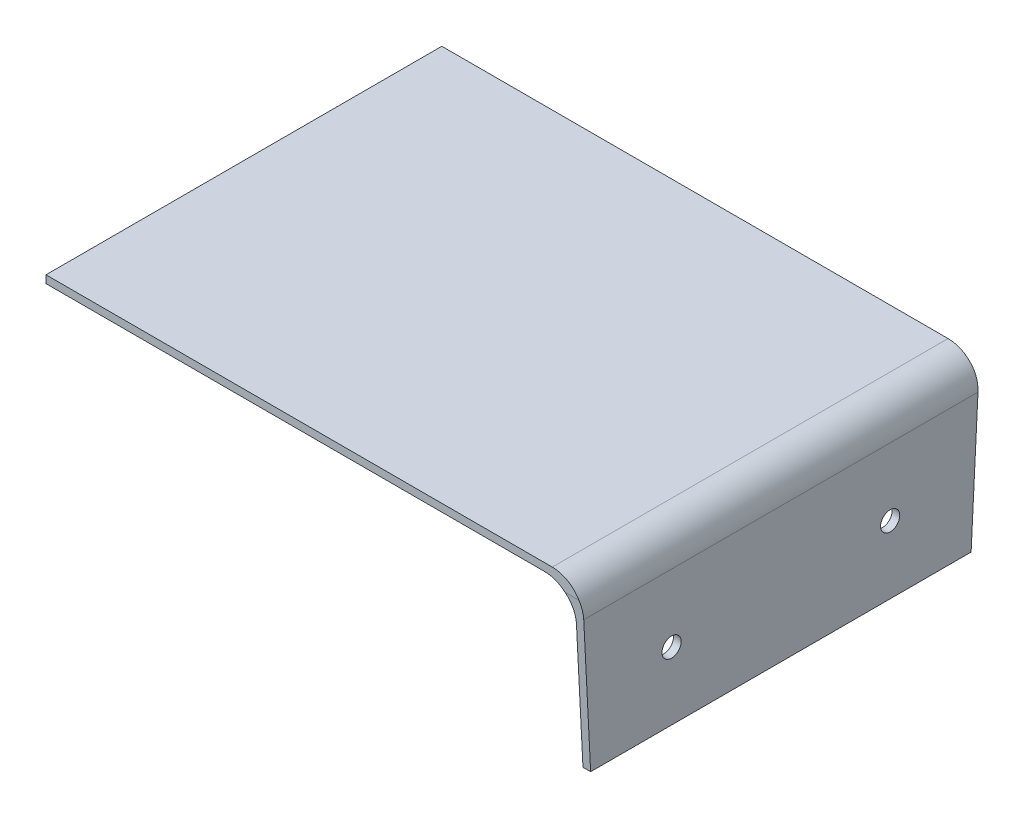
SolidWorks part; units mm, degrees
ref_plane "Front Plane" through (0, 0, 0) normal (0, 0, 1) x (1, 0, 0)
ref_plane "Top Plane" through (0, 0, 0) normal (0, 1, 0) x (1, 0, 0)
ref_plane "Right Plane" through (0, 0, 0) normal (1, 0, 0) x (0, 0, -1)
sketch "Sketch1" plane through (0, 0, 0) normal (0, 0, 1) x (1, 0, 0)
  line L0 (-22.4971, 23.5) -> (-22.4971, 22.4986)
  line L1 (42.6046, 22.4986) -> (46.5, 22.4986)
  line L2 (42.6046, 22.4986) -> (-22.4971, 22.4986)
  line L3 (46.5029, 18.5) -> (46.5029, 1.8932)
  line L4 (46.5029, 1.8932) -> (47.5029, 1.8932)
  line L5 (46.5, 22.4986) -> (46.5029, 18.5)
  line L6 (47.5029, 1.8932) -> (47.5029, 18.5)
  line L7 (-22.4971, 23.5) -> (42.5, 23.5)
  line L8 (47.5029, 18.5) -> (47.5029, 23.5)
  line L9 (47.5029, 23.5) -> (42.5, 23.5)
  dimension "D1" = 1
  dimension "D2" = 1.0014
  dimension "D3" = 70
extrude "Boss-Extrude1" add sketch "Sketch1" along normal blind 51.6
sketch "Sketch3" plane through (47.5029, 0, 0) normal (1, 0, 0) x (0, 0, -1)
  line L0 (-51.6, 21.5) -> (-51.6, 1.8932)
  line L1 (-51.6, 1.8932) -> (-51.6, 23.5) construction
  line L2 (-51.6, 1.8932) -> (-50.6, 1.8932)
  line L3 (-51.6, 1.8932) -> (0, 1.8932) construction
  line L4 (-50.6, 1.8932) -> (-51.6, 21.5)
  line L5 (0, 21.5) -> (-1, 1.8932)
  line L6 (0, 22.4986) -> (0, 18.5) construction
  line L7 (-1, 1.8932) -> (0, 1.8932)
  line L8 (0, 1.8932) -> (0, 21.5)
  line L10 (-51.6, 23.5) -> (0, 23.5) construction
  dimension "D1" = 2
  dimension "D2" = 1
  dimension "D3" = 1
  dimension "D4" = 2
extrude "Cut-Extrude1" cut sketch "Sketch3" against normal blind 10
fillet "Fillet3" radius 4 2 edges at (46.5, 22.4986, 25.8) (47.5029, 23.5, 25.8)
sketch "Sketch4" plane through (0, 22.4986, 0) normal (0, -1, 0) x (1, 0, 0)
  line L0 (-22.4971, 51.6) -> (-22.4971, 0) construction
  line L1 (-22.4971, 15) -> (-17.4971, 15)
  line L2 (-22.4971, 15) -> (-22.4971, 36.6)
  line L3 (-22.4971, 36.6) -> (-17.4971, 36.6)
  line L4 (-17.4971, 15) -> (-17.4971, 36.6)
  line L5 (-22.4971, 51.6) -> (42.5029, 51.6) construction
  line L6 (42.6046, 0) -> (-22.4971, 0) construction
  dimension "D1" = 5
  dimension "D2" = 15
  dimension "D3" = 15
extrude "Boss-Extrude2" add sketch "Sketch4" along normal blind 2.5
sketch "Sketch5" plane through (-22.4971, 0, 0) normal (-1, 0, 0) x (0, 0, 1)
  line L0 (36.6, 19.9986) -> (15, 19.9986) construction
  line L1 (36.6, 19.9986) -> (15, 19.9986)
  line L2 (36.6, 19.9986) -> (36.6, 21.4986)
  line L3 (36.6, 21.4986) -> (15, 21.4986)
  line L4 (15, 19.9986) -> (15, 21.4986)
  line L5 (15, 19.9986) -> (15, 22.4986) construction
  dimension "D1" = 1.5
extrude "Boss-Extrude3" add sketch "Sketch5" along normal blind 2
sketch "Sketch6" plane through (47.5029, 0, 0) normal (1, 0, 0) x (0, 0, -1)
  line L0 (-51.049, 10.6966) -> (-0.551, 10.6966) construction
  line L1 (-50.6, 1.8932) -> (-51.498, 19.5) construction
  line L2 (-0.102, 19.5) -> (-1, 1.8932) construction
  circle A0 centre (-40.049, 10.6966) radius 1.25
  circle A1 centre (-11.551, 10.6966) radius 1.25
  dimension "D3" = 2.5
  dimension "D1" = 11
  dimension "D2" = 11
extrude "Cut-Extrude2" cut sketch "Sketch6" against normal blind 2
